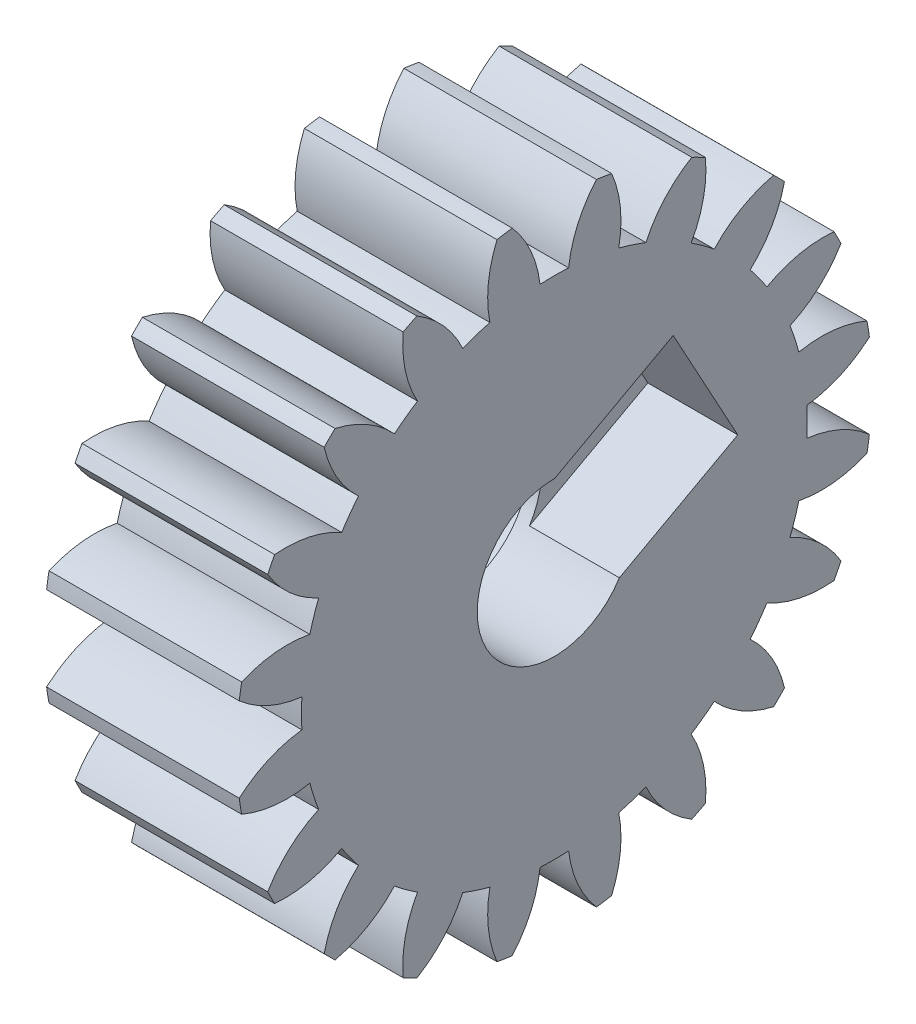
SolidWorks part; units mm, degrees
ref_plane "Plane1" through (0, 0, 0) normal (0, 0, 1) x (1, 0, 0)
ref_plane "Plane2" through (0, 0, 0) normal (0, 1, 0) x (1, 0, 0)
ref_plane "Plane3" through (0, 0, 0) normal (1, 0, 0) x (0, 0, -1)
sketch "HoldingSke" plane through (0, 0, 0) normal (0, 1, 0) x (1, 0, 0)
  line L0 (0, 0) -> (0.4176, -0.152)
  line L1 (-15, 0) -> (100, 0) construction
  line L2 (0, 0) -> (-2.1039, 2.3779)
  line L3 (0, 0) -> (-11.863, 4.5341)
  line L4 (0, 0) -> (8.1152, 2.9537)
  line L5 (0, 0) -> (-46.8476, -17.4728)
  line L6 (0, 0) -> (-8.2896, -5.593)
  line L7 (-2.1039, 2.3779) -> (8.6586, 51.2059)
  line L8 (-76.2, 54.61) -> (-76.1, 54.61)
  line L9 (-71.009, 38.7566) -> (-53.1078, 45.2721)
  line L10 (-76.2, 71.12) -> (104.1128, 71.12)
  line L11 (0, 0) -> (-10, 0)
  line L12 (-76.2, 101.6) -> (-76.123, 101.6)
  line L13 (24.9733, 27.94) -> (52.9518, 28.4284)
  line L14 (24.9733, 27.94) -> (24.9743, 27.94)
  line L15 (24.9733, 27.94) -> (100.4006, 29.5858)
  line L16 (-63.627, -2.25) -> (-12.827, -2.25)
  circle A0 centre (0, 0) radius 0.4
  circle A1 centre (0, 0) radius 19.6865
  circle A2 centre (0, 0) radius 37.5
  circle A3 centre (0, 0) radius 0.4
  dimension "MHD" = 39.373
  dimension "Hub_dia" = 75
  dimension "Bore" = 0.8
  dimension "MBD" = 0.8
  dimension "Num_teeth" = 20
  dimension "Pitch_radius" = 180.3128
  dimension "Pitch" = 0.4444
  dimension "Width" = 10
  dimension "Overall_len" = 50
  dimension "Show_teeth" = 20
  dimension "Thickness" = 10
  dimension "OAL" = 50.0001
  dimension "T_dim" = 0.1
  dimension "Ap" = 20
  dimension "H" = 19.05
  dimension "Backlash" = 0.077
  dimension "Addendum_fac" = 1
  dimension "Dedendum_fac" = 1.25
  dimension "Clearance_fac" = 0.25
  dimension "Dedendum_add" = 0.001
  dimension "Module" = 2.25
sketch "BasProSke" plane through (0, 0, 0) normal (0, 1, 0) x (1, 0, 0)
  line L0 (-10, 0) -> (60, 0) construction
  line L1 (0, 0) -> (0, 24.75)
  line L2 (0, 0) -> (15, 0)
  line L3 (15, 0) -> (15, 24.75)
  line L4 (15, 24.75) -> (0, 24.75)
  dimension "Diameter" = 49.5
  dimension "Thickness" = 15
revolve "Base-Revolve" add sketch "BasProSke" angle 360 about L0
sketch "TooCutSke" plane through (0, 0, 0) normal (1, 0, 0) x (0, 0, -1)
  line L1 (0, 0) -> (0, 107) construction
  line L2 (0, 0) -> (-1.9, 22.4196) construction
  line L3 (0, 0) -> (-7.021, 44.3291) construction
  line L4 (-1.9, 22.4196) -> (-3.5105, 22.1646) construction
  arc A0 (1.1119, 19.6551) -> (-1.1119, 19.6551) centre (0, 0) ccw
  arc A1 (3.3, 24.5546) -> (-3.3, 24.5546) centre (0, 0) ccw
  circle A2 centre (0, 0) radius 22.5 construction
  circle A3 centre (0, 0) radius 21.1431 construction
  arc A4 (-1.1119, 19.6551) -> (-3.3, 24.5546) centre (-10.0501, 18.6018) ccw
  arc A5 (3.3, 24.5546) -> (1.1119, 19.6551) centre (10.0501, 18.6018) ccw
  dimension "Root_dia" = 39.373
  dimension "Overcut_dia" = 49.5508
  dimension "Pitch_dia" = 45
  dimension "Base_dia" = 42.2862
  dimension "Flank_rad" = 9
  dimension "Half_ang" = 9
  dimension "Half_CT" = 1.6306
extrude "ToothCut" cut sketch "TooCutSke" along normal through all
fillet "Breaks" [suppressed] radius 0.045 tangent propagation no
fillet "RootFillets" [suppressed] radius 0.5635
pattern_circular "TeethCuts" count 20 over 360 about axis through (-10, 0, 0) along (1, 0, 0) of "ToothCut", "RootFillets", "Breaks"
sketch "HubNeaOneSke" plane through (0, 0, 0) normal (-1, 0, 0) x (0, 0, 1)
  circle A0 centre (0, 0) radius 19.6865
  dimension "Diameter" = 39.373
extrude "HubNearOne" [suppressed] add sketch "HubNeaOneSke" along normal blind 35.0001
sketch "HubNeaBotSke" plane through (0, 0, 0) normal (-1, 0, 0) x (0, 0, 1)
  circle A0 centre (0, 0) radius 19.6865
  dimension "Diameter" = 39.373
extrude "HubNearBoth" [suppressed] add sketch "HubNeaBotSke" along normal blind 17.5
ref_plane "FarPln" through (15, 0, 0) normal (1, 0, 0) x (0, 0, -1)
sketch "HubFarSke" plane through (15, 0, 0) normal (1, 0, 0) x (0, 0, -1)
  circle A0 centre (0, 0) radius 19.6865
  dimension "Diameter" = 39.373
extrude "HubFar" [suppressed] add sketch "HubFarSke" along normal blind 17.5
sketch "BorSke" plane through (0, 0, 0) normal (1, 0, 0) x (0, 0, -1)
  circle A0 centre (0, 0) radius 6
  dimension "Diameter" = 12
extrude "Bore" cut sketch "BorSke" along normal mid plane 100.0001
sketch "KeySke" plane through (0, 0, 0) normal (1, 0, 0) x (0, 0, -1)
  line L0 (-0.05, 0) -> (-0.05, 0.5)
  line L1 (-0.05, 0.5) -> (0.05, 0.5)
  line L2 (0.05, 0.5) -> (0.05, 0)
  line L3 (0, 0) -> (0, 34) construction
  line L4 (-0.05, 0) -> (0.05, 0)
  dimension "Offset" = 0.5
  dimension "Width" = 0.1
extrude "Keyway" [suppressed] cut sketch "KeySke" along normal mid plane 100.0001
pattern_circular "Keyway2" [suppressed] count 2 every 90 about axis through (-10, 0, 0) along (1, 0, 0) reverse direction yes
sketch "Sketch1" plane through (15, 0, 0) normal (1, 0, 0) x (0, 0, -1)
  line L0 (0.0359, 5.9999) -> (5.0641, -3.2178)
  line L1 (0.0359, 5.9999) -> (9.2536, 11.0282)
  line L2 (5.0641, -3.2178) -> (14.2819, 1.8104)
  line L3 (9.2536, 11.0282) -> (14.2819, 1.8104)
  circle A0 centre (0, 0) radius 6
  circle A1 centre (0, 0) radius 6 construction
  dimension "D1" = 0
  dimension "D4" = 12
  dimension "D2" = 6
  dimension "D3" = 6
  dimension "D5" = 10.5
  dimension "D6" = 10.5
extrude "Cut-Extrude1" cut sketch "Sketch1" against normal blind 7 contours L0 A0 | L0 A0 | A0 L0 L2 L3 L1 region at (15, 1.9994, -3.6652) region at (15, 4.4105, -8.0852) region at (15, -0.5134, 0.9411)
sketch "Sketch2" plane through (0, 0, 0) normal (-1, 0, 0) x (0, 0, 1)
  line L1 (12.4634, -6.055) -> (11.4755, 7.7661)
  line L2 (11.4755, 7.7661) -> (-0.9879, 13.8211)
  line L3 (-0.9879, 13.8211) -> (-12.4634, 6.055)
  line L4 (-12.4634, 6.055) -> (-11.4755, -7.7661)
  line L5 (-11.4755, -7.7661) -> (0.9879, -13.8211)
  line L6 (0.9879, -13.8211) -> (12.4634, -6.055)
  circle A0 centre (0, 0) radius 12 construction
  circle A1 centre (0, 0) radius 6 construction
  dimension "D1" = 0
  dimension "D2" = 24
extrude "Cut-Extrude2" cut sketch "Sketch2" against normal blind 7
equation "' \"Module@HoldingSke\" = 6.35"
equation "' \"Num_teeth@HoldingSke\" = 12"
equation "' \"Ap@HoldingSke\" =  20"
equation "' \"Width@HoldingSke\" = 0.5 * 25.4"
equation "' \"Hub_dia@HoldingSke\"= 1 * 25.4"
equation "' \"Overall_len@HoldingSke\" = 1.0 * 25.4"
equation "' \"Bore@HoldingSke\" = 0.75 * 25.4"
equation "' \"T_dim@HoldingSke\" = 0.1 * 25.4"
equation "' \"Width@KeySke\" = 0.25 * 25.4"
equation "' \"Show_teeth@HoldingSke\" = 13"
equation "' \"Backlash@HoldingSke\" = 0.009 * 25.4"
equation "' \"Addendum_fac@HoldingSke\" = 1.0"
equation "' \"Dedendum_fac@HoldingSke\" = 1.25"
equation "' \"Dedendum_add@HoldingSke\" = 0.00005 * 25.4"
equation "' \"Clearance_fac@HoldingSke\" = 0.25"
equation "\"Pitch@HoldingSke\" = 1 / \"Module@HoldingSke\""
equation "\"Overcut_dia@TooCutSke\" = (\"Num_teeth@HoldingSke\" + 2 * \"Addendum_fac@HoldingSke\") / \"Pitch@HoldingSke\" + 0.002 * 25.4"
equation "\"Pitch_dia@TooCutSke\" = \"Num_teeth@HoldingSke\" / \"Pitch@HoldingSke\""
equation "\"Base_dia@TooCutSke\" = \"Num_teeth@HoldingSke\" / \"Pitch@HoldingSke\" * cos((\"Ap@HoldingSke\"  * 3.14159265 / 180))"
equation "\"Root_dia@TooCutSke\" = (\"Num_teeth@HoldingSke\" + 2) / \"Pitch@HoldingSke\" - 2 * (\"Addendum_fac@HoldingSke\" + \"Dedendum_fac@HoldingSke\") / \"Pitch@HoldingSke\" - \"Dedendum_add@HoldingSke\" * 2"
equation "\"Half_ang@TooCutSke\" = 180 / \"Num_teeth@HoldingSke\""
equation "\"Half_CT@TooCutSke\" = \"Num_teeth@HoldingSke\" / \"Pitch@HoldingSke\" * sin((3.14159265 / 2 / \"Num_teeth@HoldingSke\")) / 2 - 7 * \"Backlash@HoldingSke\" / 4"
equation "\"Flank_rad@TooCutSke\" = \"Num_teeth@HoldingSke\" / \"Pitch@HoldingSke\" / 5"
equation "\"Radius@RootFillets\" = \"Clearance_fac@HoldingSke\" / \"Pitch@HoldingSke\" + \"Dedendum_add@HoldingSke\""
equation "\"Break_rad@Breaks\" = 0.02 / \"Pitch@HoldingSke\""
equation "\"Thickness@HoldingSke\" = \"Width@HoldingSke\""
equation "\"OAL@HoldingSke\" = \"Thickness@HoldingSke\""
equation "\"MHD@HoldingSke\" = (\"Num_teeth@HoldingSke\" + 2) / \"Pitch@HoldingSke\" - 2 * (\"Addendum_fac@HoldingSke\" + \"Dedendum_fac@HoldingSke\")  / \"Pitch@HoldingSke\" - \"Dedendum_add@HoldingSke\" * 2"
equation "\"MBD@HoldingSke\" = (\"Num_teeth@HoldingSke\" + 2) / \"Pitch@HoldingSke\" - 2 * (\"Addendum_fac@HoldingSke\" + \"Dedendum_fac@HoldingSke\")  / \"Pitch@HoldingSke\" - \"Dedendum_add@HoldingSke\" * 2 - 0.002 * 25.4"
equation "\"MHD@HoldingSke\" = ((sgn( \"MHD@HoldingSke\" - \"Hub_dia@HoldingSke\" )-1)*( \"MHD@HoldingSke\" - \"Hub_dia@HoldingSke\" ))/-2+ \"Hub_dia@HoldingSke\""
equation "\"MBD@HoldingSke\" = ((sgn( \"MBD@HoldingSke\" - \"Bore@HoldingSke\" )-1)*( \"MBD@HoldingSke\" - \"Bore@HoldingSke\" ))/-2+ \"Bore@HoldingSke\""
equation "\"OAL@HoldingSke\" = ((sgn( \"OAL@HoldingSke\" - \"Overall_len@HoldingSke\" )+1)*( \"OAL@HoldingSke\" - \"Overall_len@HoldingSke\" ))/2 + \"Overall_len@HoldingSke\" + 0.000002 * 25.4"
equation "\"Num_teeth@TeethCuts\" = int( \"Show_teeth@HoldingSke\" ) + 1"
equation "\"Num_teeth@TeethCuts\" = ((sgn( \"Num_teeth@TeethCuts\" - \"Num_teeth@HoldingSke\" )-1)*( \"Num_teeth@TeethCuts\" - \"Num_teeth@HoldingSke\" ))/-2+ \"Num_teeth@HoldingSke\""
equation "\"Num_teeth@TeethCuts\" = ((sgn( \"Num_teeth@TeethCuts\" - 2.0)+1)*( \"Num_teeth@TeethCuts\" - 2.0))/2 +2.0"
equation "\"Angle@TeethCuts\" = 360.0 / \"Num_teeth@HoldingSke\""
equation "\"Diameter@BasProSke\" = (\"Num_teeth@HoldingSke\" + 2 * \"Addendum_fac@HoldingSke\") / \"Pitch@HoldingSke\""
equation "\"Thickness@BasProSke\"=15mm"
equation "' \"Fillet_rad@BasProSke\" =  \"Thickness@HoldingSke\" * 0.05"
equation "\"MHD@HoldingSke\" = ((sgn( \"MHD@HoldingSke\" - \"Root_dia@TooCutSke\" )-1)*( \"MHD@HoldingSke\" - \"Root_dia@TooCutSke\" ))/-2+ \"Root_dia@TooCutSke\""
equation "\"Diameter@HubNeaOneSke\" = \"MHD@HoldingSke\""
equation "\"Length@HubNearOne\" = \"OAL@HoldingSke\" - \"Thickness@BasProSke\""
equation "\"Diameter@HubNeaBotSke\" = \"MHD@HoldingSke\""
equation "\"Length@HubNearBoth\" = ( \"OAL@HoldingSke\" - \"Thickness@BasProSke\" ) / 2.0"
equation "\"Thickness@FarPln\"=15"
equation "\"Diameter@HubFarSke\" = \"MHD@HoldingSke\""
equation "\"Length@HubFar\" = ( \"OAL@HoldingSke\" - \"Thickness@BasProSke\" ) / 2.0"
equation "\"Diameter@BorSke\"=12mm"
equation "\"D1@Bore\" = \"OAL@HoldingSke\" * 2.0"
equation "\"D1@Keyway\" = \"OAL@HoldingSke\" * 2.0"
equation "\"Offset@KeySke\" = \"T_dim@HoldingSke\" + \"MBD@HoldingSke\" / 2.0"
